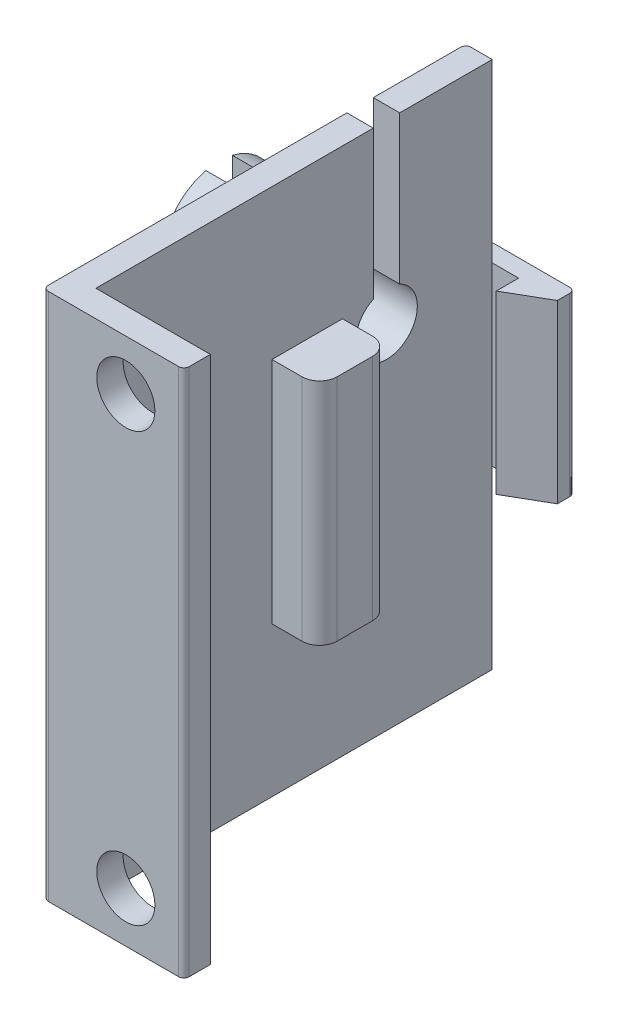
SolidWorks part; units mm, degrees
ref_plane "Front Plane" through (0, 0, 0) normal (0, 0, 1) x (1, 0, 0)
ref_plane "Top Plane" through (0, 0, 0) normal (0, 1, 0) x (1, 0, 0)
ref_plane "Right Plane" through (0, 0, 0) normal (1, 0, 0) x (0, 0, -1)
sketch "Sketch1" plane through (0, 0, 0) normal (0, 1, 0) x (1, 0, 0)
  line L0 (0, 0) -> (-2.2, 0)
  line L5 (-2.2, 0) -> (-2.2, -1.2702)
  line L6 (-2.2, -1.2702) -> (0, 0)
  dimension "D1" = 60
  dimension "D2" = 2.2
extrude "Boss-Extrude1" add sketch "Sketch1" along normal blind 5 and the other way blind 5
sketch "Sketch2" plane through (0, 0, 0) normal (0, 0, -1) x (-1, 0, 0)
  line L0 (0, 5) -> (2.2, 5) construction
  line L1 (0, -5) -> (3.7, -5)
  line L2 (0, -5) -> (0, 5)
  line L3 (0, 5) -> (3.7, 5)
  line L4 (3.7, -5) -> (3.7, 5)
  line L5 (0, -5) -> (3.7, 5) construction
  line L6 (0, 5) -> (3.7, -5) construction
  line L7 (2.2, -5) -> (2.2, 5) construction
  point P4 (1.85, 0)
  dimension "D1" = 1.5
extrude "Boss-Extrude2" add sketch "Sketch2" along normal blind 1
sketch "Sketch3" plane through (-3.7, 0, 0) normal (-1, 0, 0) x (0, 0, 1)
  line L0 (0, 0) -> (12.5427, 0) construction
  line L1 (0, -15) -> (22.5, -15)
  line L2 (0, -15) -> (0, 15)
  line L3 (0, 15) -> (22.5, 15)
  line L4 (22.5, -15) -> (22.5, 15)
  line L5 (0, -15) -> (22.5, 15) construction
  line L6 (0, 15) -> (22.5, -15) construction
  line L7 (0, -5) -> (0, 5) construction
  line L9 (0, 5) -> (-1, 5)
  line L10 (0, 5) -> (0, -5)
  line L11 (0, -5) -> (-1, -5)
  line L12 (-1, 5) -> (-1, -5)
  line L13 (0, 5) -> (-1, -5) construction
  line L14 (0, -5) -> (-1, 5) construction
  point P4 (11.25, 0)
  point P16 (-0.5, 0)
  line M6 (0, -5) -> (0, 5)
  line M7 (0, 5) -> (-1, 5)
  line M8 (-1, 5) -> (-1, -5)
  line M9 (-1, -5) -> (0, -5)
  dimension "D1" = 22.5
  dimension "D2" = 30
extrude "Boss-Extrude3" add sketch "Sketch3" along normal blind 1.5 contours L1 L4 L3 L2 M6 | M9 M6 M7 M8 region at (-3.7, 0, 11.25) region at (-3.7, 0, -0.5)
sketch "Sketch4" plane through (0, 0, 22.5) normal (0, 0, 1) x (1, 0, 0)
  line L0 (-4.45, 0) -> (3.106, 0) construction
  line L1 (-5.2, -15) -> (-3.7, -15)
  line L2 (-5.2, -15) -> (-5.2, 15)
  line L3 (-5.2, 15) -> (-3.7, 15)
  line L4 (-3.7, -15) -> (-3.7, 15)
  line L5 (-5.2, -15) -> (-3.7, 15) construction
  line L6 (-5.2, 15) -> (-3.7, -15) construction
  line L7 (-3.7, -15) -> (2.8, -15)
  line L8 (-3.7, -15) -> (-3.7, 15)
  line L9 (-3.7, 15) -> (2.8, 15)
  line L10 (2.8, -15) -> (2.8, 15)
  line L11 (-3.7, -15) -> (2.8, 15) construction
  line L12 (-3.7, 15) -> (2.8, -15) construction
  circle A0 centre (-0.5, 12.15) radius 1.65
  circle A1 centre (-0.5, -12.15) radius 1.65
  point P4 (-4.45, 0)
  point P11 (-0.45, 0)
  line M5 (-3.7, -15) -> (-3.7, 15)
  line M6 (-3.7, 15) -> (-5.2, 15)
  line M7 (-5.2, 15) -> (-5.2, -15)
  line M8 (-5.2, -15) -> (-3.7, -15)
  dimension "D4" = 3.3
  dimension "D1" = 30
  dimension "D2" = 6.5
  dimension "D3" = 3.3
  dimension "D5" = 2.85
extrude "Boss-Extrude4" add sketch "Sketch4" along normal blind 1.5 contours L7 L10 L9 M5 | M8 M5 M6 M7 region at (-4.45, 0, 22.5) region at (-0.4452, 0, 22.5)
ref_plane "Plane1" through (0, 0, 0) normal (0, 1, 0) x (1, 0, 0)
fillet "Fillet1" radius 0.3 6 edges at (-5.2, 0, -1) (-5.2, 0, 24) (-5.2, -10, 0) (-5.2, 10, 0) (2.8, 0, 24) (0, 0, -1)
sketch "Sketch5" plane through (-3.7, 0, 0) normal (1, 0, 0) x (0, 0, -1)
  line L5 (-10.5, -15) -> (-10.5, 15) construction
  line L7 (-12.5, 6.5) -> (-8.5, 6.5)
  line L8 (-12.5, 6.5) -> (-12.5, -6.5)
  line L9 (-12.5, -6.5) -> (-8.5, -6.5)
  line L10 (-8.5, 6.5) -> (-8.5, -6.5)
  line L11 (-12.5, 6.5) -> (-8.5, -6.5) construction
  line L12 (-12.5, -6.5) -> (-8.5, 6.5) construction
  line L14 (0, 15) -> (-22.5, 15) construction
  line L15 (0, 5) -> (0, 15) construction
  line L17 (0, -15) -> (-22.5, -15) construction
  point P6 (-10.5, 0)
  point P7 (-10.5, 0)
  point P12 (-10.5, 0)
  dimension "D1" = 13
  dimension "D2" = 4
  dimension "D3" = 10.5
extrude "Boss-Extrude5" add sketch "Sketch5" along normal blind 2.7 contours L8 L7 L10 L9
sketch "Sketch7" plane through (-3.7, 0, 0) normal (1, 0, 0) x (0, 0, -1)
  line L0 (0, 5) -> (0, 15) construction
  line L1 (0, 15) -> (-22.5, 15) construction
  line L2 (-6, 5) -> (-6, 15) construction
  line L3 (-6.75, 15) -> (-6.75, 6.5811)
  line L4 (-5.25, 15) -> (-5.25, 6.5811)
  line L5 (-6.75, 15) -> (-5.25, 15)
  circle A0 centre (-6, 5) radius 1.75
  circle A1 centre (-6, 5) radius 3.25
  line M6 (0, 15) -> (-22.5, 15)
  line M11 (-12.5, 6.5) -> (-8.5, 6.5)
  line M12 (-8.5, 6.5) -> (-8.5, -6.5)
  dimension "D1" = 3.5
  dimension "D6" = 1.5
  dimension "D2" = 6
  dimension "D3" = 10
  dimension "D4" = 0.75
  dimension "D5" = 1.5
extrude "Cut-Extrude1" cut sketch "Sketch7" against normal through all contours A0 | A1 L2 L5 L3 | L2 A1 L4 M6 | L2 A0 L4 A1 | A0 L2 A1 L3 region at (-3.7, 7.4573, 6.3783) region at (-3.7, 7.4573, 5.6217) region at (-3.7, 6.659, 5.6265) region at (-3.7, 11.6104, 6.3758) region at (-3.7, 11.6104, 5.6242)
extrude "Boss-Extrude6" add sketch "Sketch7<3>" against normal blind 8 from surface contours L3 A1 L4 A0 | A1 M11 M12 region at (-3.7, 7.3717, 6.8387) region at (-3.7, 4.8994, 8.8133) starting at face at (-5.2, 3.3193, 5.9333)
sketch "Sketch7<3>" plane through (-3.7, 0, 0) normal (1, 0, 0) x (0, 0, -1) same geometry as "Sketch7"
ref_plane "Plane2" through (0, 1.75, 0) normal (0, -1, 0) x (-1, 0, 0)
sketch "Sketch8" plane through (0, 1.75, 0) normal (0, -1, 0) x (-1, 0, 0)
  line L0 (13.2, -2.75) -> (5.2, -2.75) construction
  line L1 (13.2, -2.75) -> (8.4, -2.75)
  line L2 (13.2, -2.75) -> (13.2, -9.25)
  line L3 (13.2, -9.25) -> (8.4, -9.25)
  line L4 (8.4, -2.75) -> (8.4, -9.25)
  line L5 (13.2, -2.75) -> (8.4, -9.25) construction
  line L6 (13.2, -9.25) -> (8.4, -2.75) construction
  line L7 (13.2, -9.25) -> (13.2, -2.75) construction
  point P4 (10.8, -6)
  dimension "D1" = 4.8
ref_axis "Axis1" through (-13.2, 5, 6) along (1, 0, 0)
ref_plane "Plane3" through (0, 5, 0) normal (0, 1, 0) x (1, 0, 0)
extrude "Cut-Extrude2" cut sketch "Sketch8" against normal up to surface (3.25 mm away) up to plane "Plane3"
fillet "Fillet4" radius 1 2 edges at (-1, 0, 12.5) (-1, 0, 8.5)
chamfer "Chamfer1" distance 2 angle 45 2 edges at (-8.4, 5, 8.5) (-8.4, 5, 3.5)
chamfer "Chamfer3" distance 1 angle 45 1 edges at (-5.2, 1.75, 6)
equation "\"WallThick\"= 1.2'thickness of wall for printer"
equation "\"dHole\"= 3.3'diameter of screw hole"
equation "\"dCable\"= 1.5"
equation "\"FillHole\"= 8'Height of fill hole to seal with hot glue"
equation "\"D1@Sketch8\"=0.6*\"FillHole\""
equation "\"D1@Boss-Extrude6\"=\"FillHole\""
